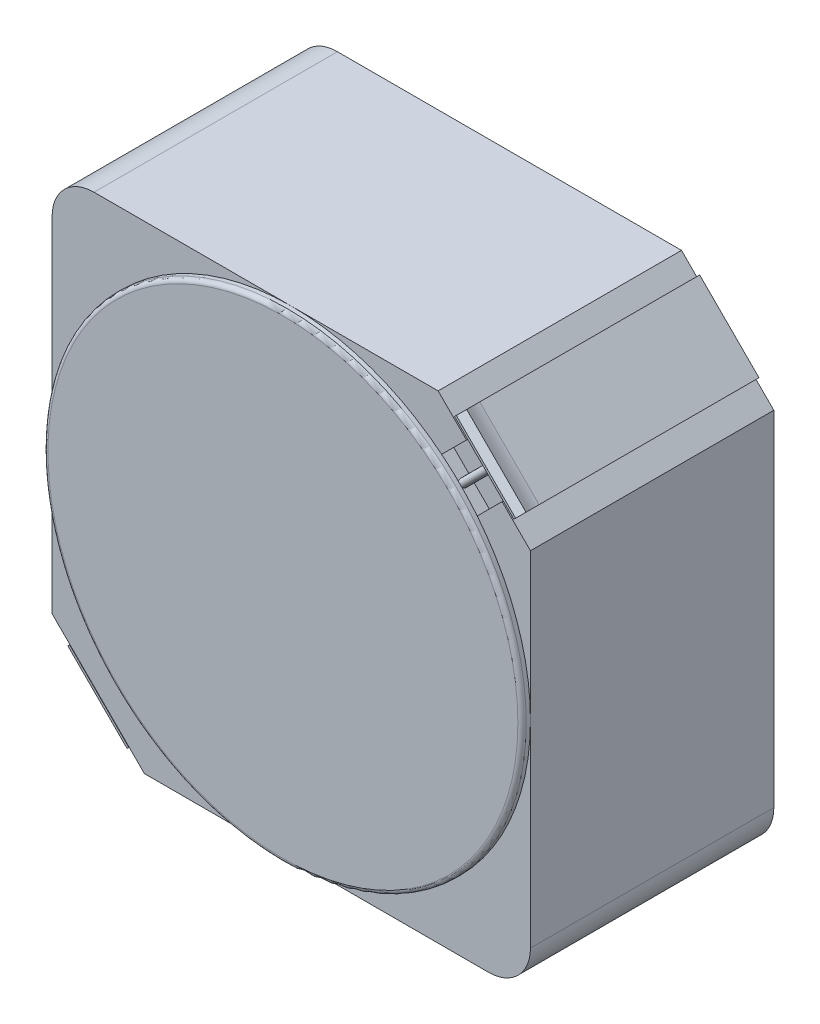
SolidWorks part; units mm, degrees
ref_plane "Спереди" through (0, 0, 0) normal (0, 0, 1) x (1, 0, 0)
ref_plane "Сверху" through (0, 0, 0) normal (0, 1, 0) x (1, 0, 0)
ref_plane "Справа" through (0, 0, 0) normal (1, 0, 0) x (0, 0, -1)
sketch "Эскиз1" plane through (0, 0, 0) normal (0, 0, 1) x (1, 0, 0)
  line L0 (-2.85, -1.75) -> (-1.75, -2.85)
  line L1 (-2.35, 2.85) -> (1.75, 2.85)
  line L2 (-2.85, 2.35) -> (-2.85, -1.75)
  line L3 (-1.75, -2.85) -> (2.35, -2.85)
  line L4 (2.85, 1.75) -> (2.85, -2.35)
  line L5 (-2.85, 2.85) -> (2.85, -2.85) construction
  line L6 (-2.85, -2.85) -> (2.85, 2.85) construction
  line L7 (1.75, 2.85) -> (2.85, 1.75)
  arc A0 (-2.35, 2.85) -> (-2.85, 2.35) centre (-2.35, 2.35) ccw
  arc A1 (2.35, -2.85) -> (2.85, -2.35) centre (2.35, -2.35) ccw
  point P0 (0, 0)
  dimension "D1" = 0.5
  dimension "D2" = 5.7
extrude "Корпус" add sketch "Эскиз1" along normal blind 2.9 from offset 0.005
sketch "Эскиз2" plane through (0, 0, 2.905) normal (0, 0, 1) x (1, 0, 0)
  line L0 (-2.85, 2.35) -> (-2.85, -1.75) construction
  circle A0 centre (0, 0) radius 2.85
extrude "Серлечник" add sketch "Эскиз2" along normal blind 0.1 and the other way blind 1
fillet "Скругление1" radius 0.05 1 edges at (2.85, 0, 3.005)
ref_plane "Плоскость1" through (0.55, -0.55, 0) normal (0.7071, -0.7071, 0) x (0, 0, 1)
sketch "Эскиз6" plane through (0.55, -0.55, 0) normal (0.7071, -0.7071, 0) x (0, 0, 1)
  line L0 (2.813, -3.3477) -> (2.9, -3.2957)
  line L1 (2.9, -3.2657) -> (0.03, -3.2657)
  line L2 (2.62, -3.2957) -> (0, -3.2957)
  line L3 (0, -3.2957) -> (0, -2.7657)
  line L4 (0.03, -3.2657) -> (0.03, -2.7657)
  line L5 (0.03, -2.7657) -> (0, -2.7657)
  line L6 (2.9, -3.2957) -> (2.9, -3.2657)
  line L8 (0.005, -3.2527) -> (2.905, -3.2527) construction
  line L9 (2.905, -2.85) -> (2.905, -2.0153) construction
  line L11 (0.005, 0.3536) -> (0.005, 3.2527) construction
  line L12 (2.905, -3.2527) -> (0.005, -3.2527) construction
  spline S0 degree 2 poles (2.62, -3.2957) (2.7238, -3.2995) (2.813, -3.3477) knots 0 0 0 1 1 1
  point P8 (0, 0)
  point P15 (0, -2.73)
  point P17 (2.89, -2.566)
  point P21 (0, 0)
  point P22 (0, -2.73)
  dimension "D2" = 0.5
  dimension "D3" = 0.013
  dimension "D4" = 0.025
  dimension "D5" = 0.005
  dimension "D6" = 0.082
  dimension "D7" = 0.087
  dimension "D8" = 120.867
  dimension "D9" = 0.28
  dimension "D10" = 0.1354
  dimension "D11" = 0.0295
  dimension "D12" = 0.03
extrude "вывод, бок" add sketch "Эскиз6" against normal blind 1 from offset 0.3 offset against normal yes
ref_point "Точка1"
ref_axis "Ось1" through (0, 0, 3.005) along (0, 0, -1)
sketch "Эскиз8" plane through (0, 0, 2.905) normal (0, 0, 1) x (1, 0, 0)
  line L0 (2.5121, 2.0879) -> (2.0879, 2.5121)
  line L2 (2.0879, 2.5121) -> (1.7357, 2.16)
  line L3 (-1.6879, -2.1121) -> (-1.3425, -1.7534)
  line L4 (1.9479, 1.9479) -> (0, 0) construction
  line L5 (2.5121, 2.0879) -> (2.16, 1.7357)
  line L6 (2.16, 1.7357) -> (1.7357, 2.16)
  line L7 (-1.7748, -1.3372) -> (-1.3425, -1.7534)
  line L8 (-2.1201, -1.696) -> (-1.7748, -1.3372)
  line L9 (-2.1201, -1.696) -> (-1.6879, -2.1121)
  line L10 (2.85, 1.75) -> (1.75, 2.85) construction
  point P3 (1.4809, 1.4964)
  point P6 (-1.5479, 1.5479)
  dimension "D2" = 0.498
  dimension "D4" = 0.6
  dimension "D1" = 2
extrude "Вытянуть8" cut sketch "Эскиз8" against normal blind 0.2
sketch "Эскиз9" plane through (2.3092, 2.3092, 0) normal (-0.7071, -0.7071, 0) x (0, 0, 1)
  line L1 (0, 0) -> (2.804, 0) construction
  line L2 (2.9, 0.5222) -> (2.9, -0.4778) construction
  circle A0 centre (2.804, 0) radius 0.046
  point P2 (-0.2219, 0)
  point P3 (2.6811, 0)
  point P4 (2.8564, 0)
  point P5 (0, 0)
  point P6 (-3.43, -0.4201)
  point P7 (-3.5378, -0.674)
  dimension "D1" = 0.092
  dimension "D2" = 0.096
extrude "Бобышка-Вытянуть1" add sketch "Эскиз9" along normal up to next (0.511 mm away) and the other way blind 0.05 draft 45 from offset 0.05 other way draft outward yes
pattern_circular "Круговой массив3" count 2 over 360 about axis through (0, 0, 3.005) along (0, 0, -1) of "вывод, бок", "Бобышка-Вытянуть1"
sketch "Эскиз13" plane through (0, 0, 0.005) normal (0, 0, -1) x (-1, 0, 0)
  line L1 (-2.85, -2.35) -> (-2.85, 1.75) construction
  line L2 (0, -2.8) -> (0, 0) construction
  line L3 (2.85, 2.35) -> (2.85, -1.75) construction
  line L4 (1.9308, -2.6692) -> (1.75, -2.85) construction
  line L5 (55, 0) -> (-55, 0) construction
  line L6 (2.2, 1.1488) -> (2.8, 1.1488)
  line L7 (1.75, -2.85) -> (-2.35, -2.85) construction
  line L8 (2.8, 1.1488) -> (2.8, 1.7288)
  line L9 (1.7288, 2.8) -> (2.8, 1.7288)
  line L10 (-1.7288, 2.8) -> (1.7288, 2.8)
  line L11 (-2.8, 1.7288) -> (-1.7288, 2.8)
  line L12 (-2.8, -1.1488) -> (-2.2, -1.1488)
  line L13 (-2.8, -1.7288) -> (-2.8, -1.1488)
  line L16 (-2.8, -1.7288) -> (-1.7288, -2.8)
  line L17 (-2.8, 1.7288) -> (-2.8, 1.1488)
  line L18 (-1.7288, -2.8) -> (1.7288, -2.8)
  line L19 (1.7288, -2.8) -> (2.8, -1.7288)
  line L20 (2.8, -1.1488) -> (2.8, -1.7288)
  line L21 (2.2, -1.1488) -> (2.8, -1.1488)
  line L22 (-2.8, 1.1488) -> (-2.2, 1.1488)
  arc A0 (-2.2, -1.1488) -> (2.2, -1.1488) centre (0, 0) ccw
  arc A1 (-2.2, 1.1488) -> (2.2, 1.1488) centre (0, 0) cw
  point P3 (0, -0.7488)
  point P5 (0, -0.7488)
  point P6 (0, -0.7488)
  point P7 (0, 0)
  dimension "D5" = 0.05
  dimension "D6" = 0.0503
  dimension "D7" = 0.05
  dimension "D8" = 0.6
  dimension "D1" = 0.58
extrude "Выводы низ" add sketch "Эскиз13" along normal up to surface (0.005 mm away) up to face at (-2.1273, -2.1587, 0)
